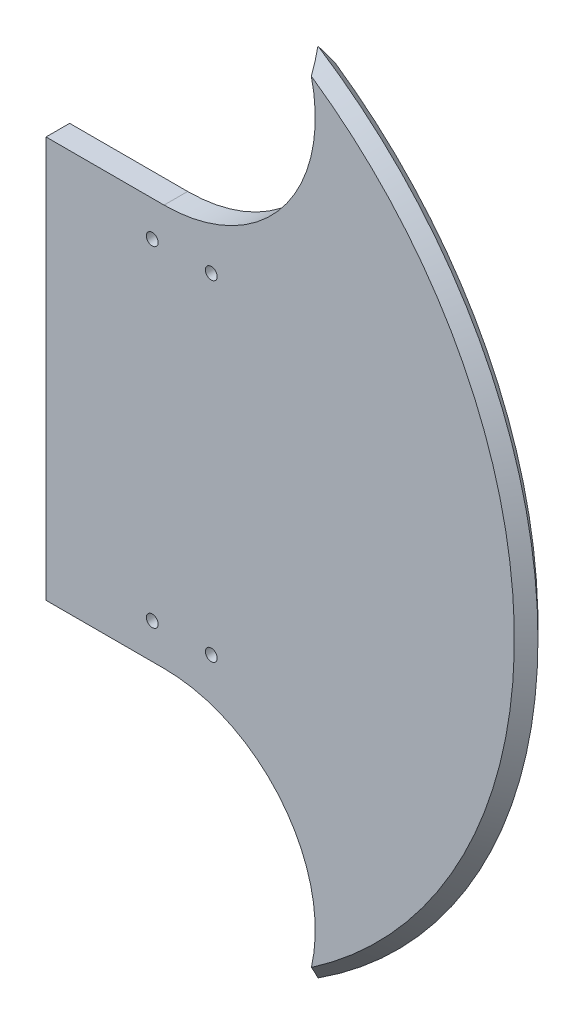
SolidWorks part; units mm, degrees
ref_plane "Спереди" through (0, 0, 0) normal (0, 0, 1) x (1, 0, 0)
ref_plane "Сверху" through (0, 0, 0) normal (0, 1, 0) x (1, 0, 0)
ref_plane "Справа" through (0, 0, 0) normal (1, 0, 0) x (0, 0, -1)
sketch "Эскиз1" plane through (0, 0, 0) normal (0, 0, 1) x (1, 0, 0)
  line L0 (0, 0) -> (170.2485, 0) construction
  line L1 (0, -85) -> (0, 85)
  line L2 (0, 85) -> (50, 85)
  line L3 (0, -85) -> (50, -85)
  arc A0 (50, 85) -> (110.1874, 170.9565) centre (50, 149.0501) ccw
  arc A1 (50, -85) -> (110.1874, -170.9565) centre (50, -149.0501) cw
  arc A2 (110.1874, -170.9565) -> (110.1874, 170.9565) centre (0, 0) ccw
  dimension "D1" = 250
  dimension "D2" = 170
  dimension "D3" = 50
  dimension "D4" = 114.394
extrude "Бобышка-Вытянуть1" add sketch "Эскиз1" along normal blind 10
chamfer "Фаска2" distance 5 angle 45 2 edges at (203.3898, 0, 0) (203.3898, 0, 10)
sketch "Эскиз2" plane through (0, 0, 10) normal (0, 0, 1) x (1, 0, 0)
  line L0 (0, 0) -> (226.9348, 0) construction
  line L1 (0, 85) -> (0, -85) construction
  circle A0 centre (45, -70) radius 2.5
  circle A1 centre (70, -70) radius 2.5
  circle A2 centre (70, 70) radius 2.5
  circle A3 centre (45, 70) radius 2.5
  dimension "D1" = 5
  dimension "D2" = 5
  dimension "D3" = 25
  dimension "D4" = 70
  dimension "D5" = 70
  dimension "D6" = 70
extrude "Вырез-Вытянуть1" cut sketch "Эскиз2" against normal blind 30
